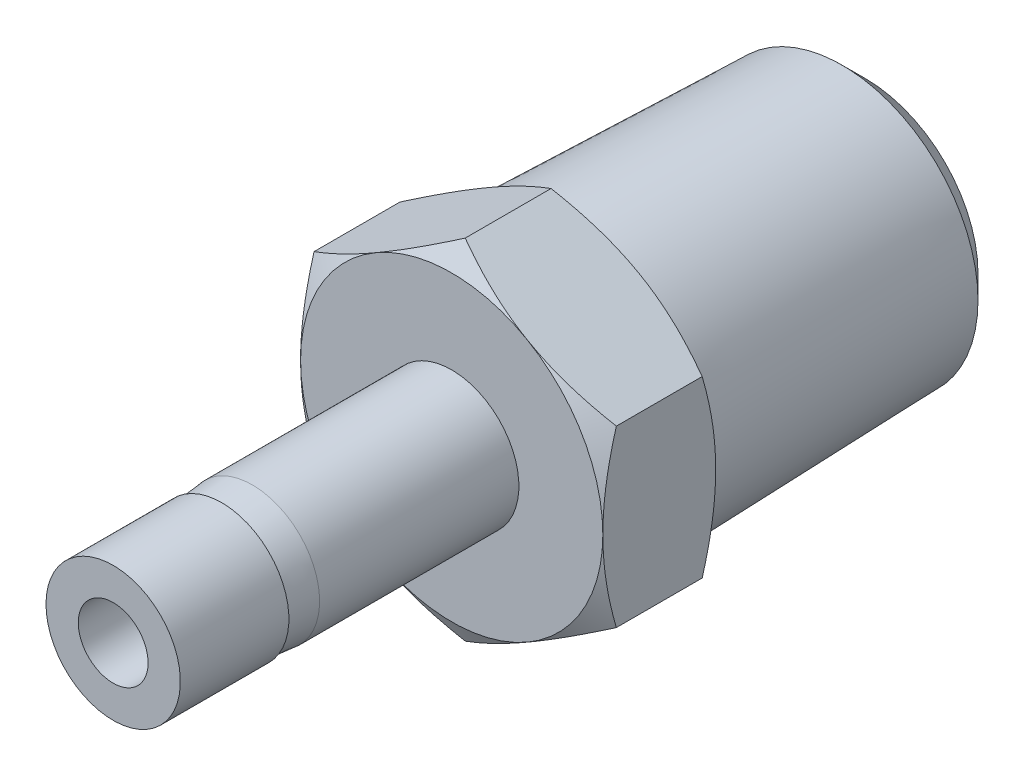
SolidWorks part; units mm, degrees
material "AISI 316 Stainless Steel Sheet (SS)"
ref_plane "Front Plane" through (0, 0, 0) normal (0, 0, 1) x (1, 0, 0)
ref_plane "Top Plane" through (0, 0, 0) normal (0, 1, 0) x (1, 0, 0)
ref_plane "Right Plane" through (0, 0, 0) normal (1, 0, 0) x (0, 0, -1)
sketch "Sketch1" plane through (0, 0, 0) normal (1, 0, 0) x (0, 0, -1)
  line L0 (0, 0) -> (35.56, 0) construction
  line L4 (0, 3.175) -> (0, -3.175) construction
  line L5 (21.336, 7.1437) -> (21.336, -7.1437) construction
  line L7 (0, 3.175) -> (5.1308, 3.175) construction
  line L14 (21.336, 1.651) -> (21.336, -1.651) construction
  line L21 (35.56, 6.3878) -> (35.56, -6.3878) construction
  line L22 (20.4572, 6.858) -> (20.4572, -6.858) construction
  line L23 (20.4572, 6.858) -> (35.56, 6.3878) construction
  line L24 (20.4572, 6.858) -> (20.4572, 5.4469) construction
  line L25 (25.3543, 6.7055) -> (25.3543, -6.7055) construction
  line L26 (35.56, 4.6228) -> (35.56, -4.6228) construction
  point P15 (16.002, 0)
  point P33 (21.336, 0)
  point P40 (20.4572, 0)
  point P44 (25.3543, 0)
  dimension "R" = 14.224
sketch "Sketch2" plane through (0, 0, 0) normal (1, 0, 0) x (0, 0, -1)
  line L0 (5.1308, 3.175) -> (5.1308, 3.048)
  line L1 (16.002, 0) -> (0, 0)
  line L2 (16.002, 0) -> (16.002, 3.175)
  line L3 (16.002, 3.175) -> (6.5824, 3.175)
  line L4 (0, 0) -> (0, 3.175)
  line L5 (5.1308, 3.048) -> (6.5824, 3.175)
  line L6 (5.1308, 3.175) -> (0, 3.175)
  dimension "D1" = 5
  dimension "D2" = 0.127
revolve "Revolve1" add sketch "Sketch2" angle 360 about L1
sketch "Sketch3" plane through (0, 0, -16.002) normal (0, 0, -1) x (-1, 0, 0)
  line L0 (0, 0) -> (0, 8.2489) construction
  line L1 (0, 8.2489) -> (-7.1437, 4.1244)
  line L2 (-7.1437, 4.1244) -> (-7.1438, -4.1244)
  line L3 (-7.1438, -4.1244) -> (0, -8.2489)
  line L4 (0, -8.2489) -> (7.1437, -4.1244)
  line L5 (7.1437, -4.1244) -> (7.1438, 4.1244)
  line L6 (7.1438, 4.1244) -> (0, 8.2489)
  circle A0 centre (0, 0) radius 7.1438 construction
extrude "Boss-Extrude1" add sketch "Sketch3" along normal up to vertex (5.334 mm away) up to point (0, 0, -21.336)
sketch "Sketch4" plane through (0, 0, 0) normal (1, 0, 0) x (0, 0, -1)
  line L0 (21.336, 8.2489) -> (16.002, 8.2489) construction
  line L1 (21.336, 8.2489) -> (21.336, 4.1244) construction
  line L2 (16.002, 8.2489) -> (16.002, 7.1438)
  line L3 (16.002, 8.2489) -> (16.002, 4.1244) construction
  line L4 (16.002, 7.1438) -> (16.6401, 8.2489)
  line L5 (16.6401, 8.2489) -> (20.6979, 8.2489)
  line L7 (21.336, 7.1438) -> (20.6979, 8.2489)
  line L8 (21.336, 8.2489) -> (21.336, 4.1244) construction
  line L10 (0, 3.175) -> (0, -3.175) construction
  line L11 (0, 0) -> (21.336, 0)
  line L12 (0, 0) -> (0, 1.651)
  line L13 (0, 1.651) -> (21.336, 1.651)
  line L14 (16.002, 8.2489) -> (16.002, 9.354)
  line L15 (16.002, 9.354) -> (21.336, 9.354)
  line L16 (21.336, 9.354) -> (21.336, 8.2489)
  line L17 (21.336, 8.2489) -> (21.336, 7.1438)
  line L18 (21.336, 0) -> (21.336, 1.651)
  dimension "D1" = 30
revolve "Cut-Revolve1" cut sketch "Sketch4" angle 360 about L0
sketch "Sketch5" plane through (0, 0, 0) normal (1, 0, 0) x (0, 0, -1)
  line L0 (20.4572, 0) -> (35.56, 0)
  line L1 (35.56, 0) -> (35.56, 6.3878)
  line L2 (35.56, 6.3878) -> (20.4572, 6.858)
  line L3 (20.4572, 6.858) -> (20.4572, 0)
revolve "Revolve2" add sketch "Sketch5" angle 360 about L0
sketch "Sketch6" plane through (0, 0, -35.56) normal (0, 0, -1) x (-1, 0, 0)
  circle A1 centre (0, 0) radius 6.3878
  circle A2 centre (0, 0) radius 6.3878
  point P0 (0, 6.3878)
  dimension "D1" = 0
curve "Helix/Spiral1" [suppressed]
sketch "Sketch7" plane through (0, 0, 0) normal (1, 0, 0) x (0, 0, -1)
  line L0 (35.4718, 6.5405) -> (36.8829, 6.5405) construction
  line L1 (35.4718, 6.5405) -> (36.1774, 5.3185) construction
  line L2 (36.1774, 5.3185) -> (36.8829, 6.5405) construction
  line L3 (36.0892, 5.4712) -> (36.2656, 5.4712) construction
  line L4 (35.56, 6.3878) -> (36.7947, 6.3878) construction
  line L5 (36.1774, 5.3185) -> (36.1774, 5.4712) construction
  line L6 (36.1774, 6.3878) -> (36.1774, 6.5405) construction
  line L7 (36.1774, 6.4642) -> (36.8388, 6.4642) construction
  line L8 (36.1774, 5.3185) -> (36.1774, -6.3686) construction
  line L9 (36.1774, -6.3686) -> (34.7669, -6.4125) construction
  line L10 (34.7669, -6.4125) -> (33.3565, -6.4564) construction
  line L11 (33.3565, -6.4564) -> (31.9461, -6.5003) construction
  line L12 (35.4718, 6.5405) -> (36.8388, 6.4642)
  line L13 (36.8388, 6.4642) -> (36.2656, 5.4712)
  line L14 (36.2656, 5.4712) -> (36.0892, 5.4712)
  line L15 (36.0892, 5.4712) -> (35.4718, 6.5405)
  line L16 (20.4572, -6.858) -> (35.56, -6.3878) construction
  line L17 (31.9461, -6.5003) -> (30.5357, -6.5442) construction
  line L18 (30.5357, -6.5442) -> (29.1252, -6.5881) construction
  dimension "D1" = 1.4111
  dimension "D2" = 0.1764
sweep "Cut-Sweep1" [suppressed] cut profiles "Sketch7" path "Helix/Spiral1"
combine bodies "Combine1" operation type add bodies to combine 113 121
sketch "Sketch8" plane through (0, 0, 0) normal (1, 0, 0) x (0, 0, -1)
  line L0 (36.1774, 5.3185) -> (35.56, 5.3185) construction
  line L5 (35.56, 6.3878) -> (35.56, -6.3878) construction
  line L6 (35.56, 5.3185) -> (34.3379, 6.5405)
  line L7 (34.3379, 6.5405) -> (35.56, 6.5405)
  line L8 (35.56, 6.5405) -> (35.56, 5.3185)
  line L9 (35.4718, 6.5405) -> (36.8829, 6.5405) construction
  line L10 (35.56, 4.6228) -> (20.4572, 4.6228)
  line L11 (20.4572, 4.6228) -> (20.4572, 0) construction
  line L12 (17.6795, 0) -> (35.56, 0)
  line L13 (17.6795, 0) -> (20.4572, 4.6228)
  line L14 (35.56, 0) -> (35.56, 4.6228)
  dimension "D1" = 59
revolve "Cut-Revolve2" cut sketch "Sketch8" angle 360 about L0
equation "\"D4@Helix/Spiral1\" = \"Pipe Pitch@Sketch1\""
equation "\"D3@Helix/Spiral1\" = \"D4@Helix/Spiral1\" + \"L4@Sketch1\""
equation "\"D1@Sketch7\" = \"D4@Helix/Spiral1\""
equation "\"D2@Sketch7\" = \"D1@Sketch7\" / 8"
